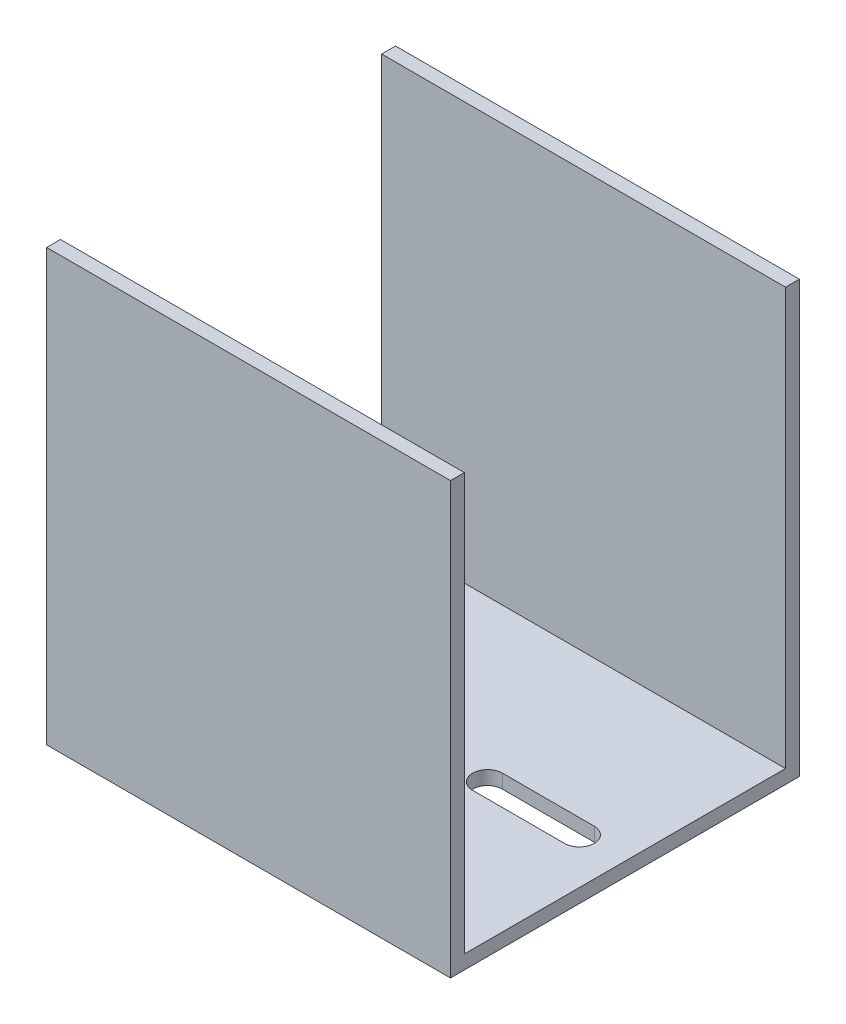
SolidWorks part; units mm, degrees
ref_plane "Front Plane" through (0, 0, 0) normal (0, 0, 1) x (1, 0, 0)
ref_plane "Top Plane" through (0, 0, 0) normal (0, 1, 0) x (1, 0, 0)
ref_plane "Right Plane" through (0, 0, 0) normal (1, 0, 0) x (0, 0, -1)
sketch "Sketch1" plane through (0, 0, 0) normal (0, 1, 0) x (1, 0, 0)
  line L0 (0, -4.8) -> (139.7, -4.8)
  line L1 (0, 0) -> (139.7, 0)
  line L2 (0, 0) -> (0, -120.7)
  line L3 (0, -120.7) -> (139.7, -120.7)
  line L4 (139.7, 0) -> (139.7, -120.7)
  line L5 (0, -115.9) -> (139.7, -115.9)
  line L6 (92.1, -55.15) -> (123.9, -55.15)
  line L7 (92.1, -65.45) -> (123.9, -65.45)
  line L8 (7.55, -20.6) -> (7.55, -33.3)
  line L9 (17.85, -20.6) -> (17.85, -33.3)
  line L10 (17.85, -87.3) -> (17.85, -100)
  line L11 (7.55, -87.3) -> (7.55, -100)
  circle A0 centre (12.7, -60.3) radius 5.15
  circle A1 centre (39.7, -60.3) radius 5.15
  circle A2 centre (92.1, -60.3) radius 5.15
  circle A3 centre (123.9, -60.3) radius 5.15
  circle A4 centre (12.7, -20.6) radius 5.15
  circle A5 centre (12.7, -33.3) radius 5.15
  circle A6 centre (12.7, -87.3) radius 5.15
  circle A7 centre (12.7, -100) radius 5.15
  point P35 (4.253, -96.6476)
  point P36 (0, 0)
  point P37 (0, 0)
  point P38 (0, 0)
  point P41 (0, 0)
  point P42 (0, 0)
  point P43 (0, 0)
  dimension "D4" = 31.8
  dimension "10.3" = 10.3
  dimension "D1" = 139.7
  dimension "D2" = 120.7
  dimension "D3" = 4.8
  dimension "4.8" = 4.8
  dimension "55.6" = 55.6
  dimension "27" = 27
  dimension "D5" = 12.7
  dimension "79.4" = 79.4
  dimension "D6" = 27
  dimension "D7" = 27
  dimension "D8" = 12.7
  dimension "12.7" = 12.7
extrude "Boss-Extrude1" add sketch "Sketch1" along normal blind 4.8 contours L2 L5 L4 L0 A7 L11 A6 L10 A5 L8 A4 L9 A3 L7 A2 L6 A1 A0 region at (70.9575, 0, 60.3535)
extrude "Boss-Extrude2" add sketch "Sketch1<4>" along normal blind 149 contours L5 L2 L3 L4 | L4 L1 L2 L0 region at (69.85, 0, 2.4) region at (69.85, 0, 118.3)
sketch "Sketch1<4>" plane through (0, 0, 0) normal (0, 1, 0) x (1, 0, 0) same geometry as "Sketch1"
